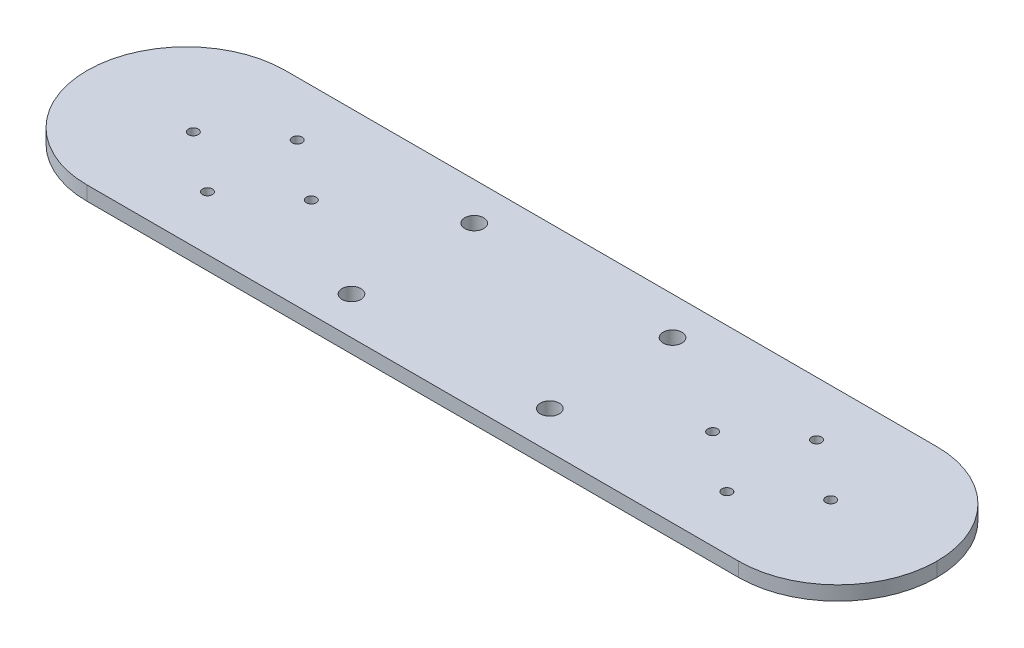
SolidWorks part; units mm, degrees
ref_plane "前视基准面" through (0, 0, 0) normal (0, 0, 1) x (1, 0, 0)
ref_plane "上视基准面" through (0, 0, 0) normal (0, 1, 0) x (1, 0, 0)
ref_plane "右视基准面" through (0, 0, 0) normal (1, 0, 0) x (0, 0, -1)
sketch "草图1" plane through (0, 0, 0) normal (0, 0, 1) x (1, 0, 0)
  line L1 (-90, -1.5) -> (90, -1.5)
  line L2 (-90, -1.5) -> (-90, 1.5)
  line L3 (-90, 1.5) -> (90, 1.5)
  line L4 (90, -1.5) -> (90, 1.5)
  line L5 (-90, -1.5) -> (90, 1.5) construction
  line L6 (-90, 1.5) -> (90, -1.5) construction
  point P0 (0, 0)
  dimension "D1" = 3
  dimension "D2" = 180
extrude "凸台-拉伸1" add sketch "草图1" along normal mid plane 42
sketch "草图2" plane through (0, 1.5, 0) normal (0, 1, 0) x (1, 0, 0)
  line L0 (-21, 13) -> (21, 13) construction
  line L1 (21, 13) -> (21, -13) construction
  line L2 (21, -13) -> (-21, -13) construction
  line L3 (-21, -13) -> (-21, 13) construction
  circle A0 centre (-21, 13) radius 2
  circle A1 centre (21, 13) radius 2
  circle A2 centre (21, -13) radius 2
  circle A3 centre (-21, -13) radius 2
  point P8 (21, 0)
  point P9 (0, 13)
  dimension "D1" = 4
  dimension "D2" = 42
  dimension "D3" = 26
extrude "切除-拉伸1" cut sketch "草图2" against normal through all
sketch "草图3" plane through (0, 1.5, 0) normal (0, 1, 0) x (1, 0, 0)
  circle A0 centre (55, 0) radius 9.5 construction
  circle A1 centre (55, 0) radius 12.5 construction
  circle A2 centre (55, 9.5) radius 1.05
  circle A3 centre (55, -9.5) radius 1.05
  circle A4 centre (42.5, 0) radius 1.05
  circle A5 centre (67.5, 0) radius 1.05
  dimension "D1" = 25
  dimension "D2" = 19
  dimension "D4" = 2.1
  dimension "D3" = 55
extrude "切除-拉伸2" cut sketch "草图3" against normal through all
mirror "镜向1" about plane through (0, 0, 0) normal (1, 0, 0) of "切除-拉伸2"
fillet "圆角1" radius 21 4 edges at (90, 0, 21) (-90, 0, 21) (-90, 0, -21) (90, 0, -21)
